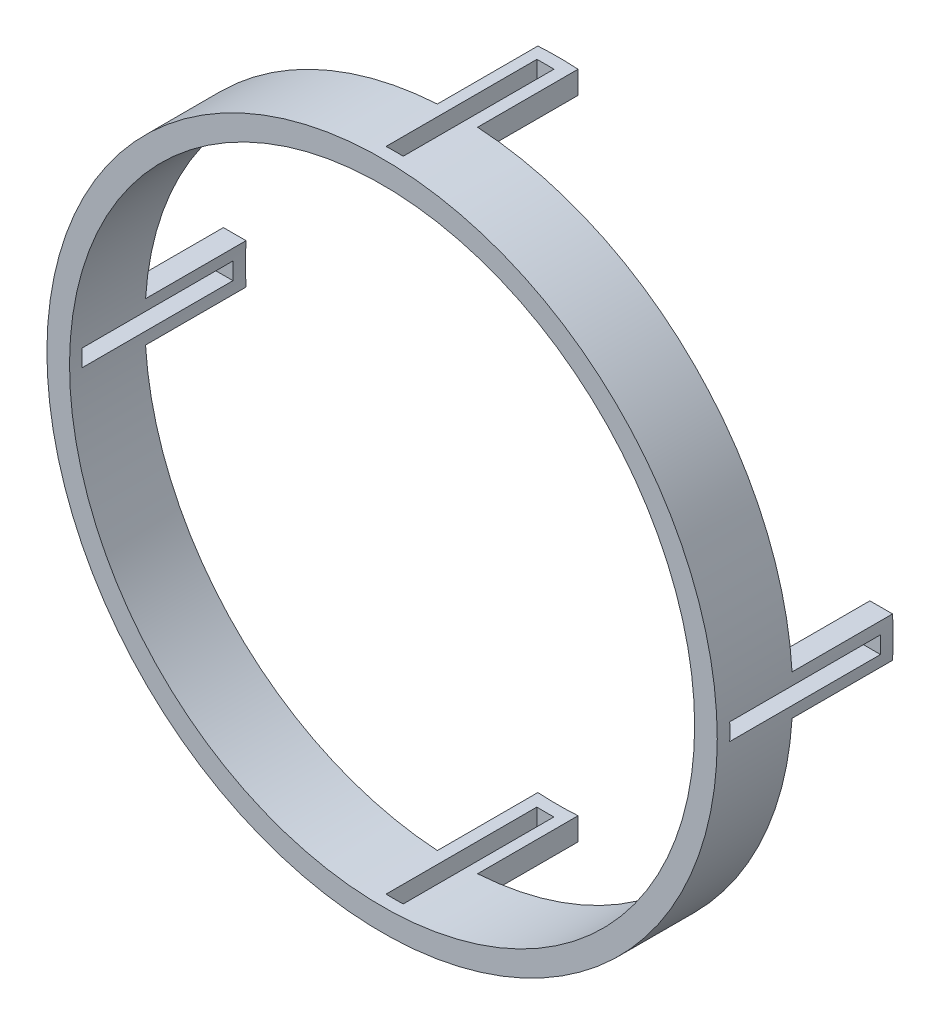
SolidWorks part; units mm, degrees
ref_plane "Front Plane" through (0, 0, 0) normal (0, 0, 1) x (1, 0, 0)
ref_plane "Top Plane" through (0, 0, 0) normal (0, 1, 0) x (1, 0, 0)
ref_plane "Right Plane" through (0, 0, 0) normal (1, 0, 0) x (0, 0, -1)
sketch "Sketch1" plane through (0, 0, 0) normal (0, 0, 1) x (1, 0, 0)
  circle A0 centre (0, 0) radius 78.994
  circle A1 centre (0, 0) radius 84.709
  dimension "D1" = 157.988
  dimension "D2" = 169.418
extrude "Boss-Extrude1" add sketch "Sketch1" along normal blind 19.05
sketch "Sketch3" plane through (0, 0, 0) normal (0, 0, -1) x (-1, 0, 0)
  line L0 (30.8173, 0) -> (-22.3005, 0) construction
  line L1 (0, -12.9993) -> (0, 95.4691) construction
  line L2 (-5.08, 78.8305) -> (-5.08, 84.5565)
  line L3 (5.08, 78.8305) -> (5.08, 84.5565)
  line L4 (-5.08, -78.8305) -> (-5.08, -84.5565)
  line L5 (5.08, -78.8305) -> (5.08, -84.5565)
  line L6 (0, 0) -> (44.2484, -44.2484) construction
  line L7 (78.8305, -5.08) -> (84.5565, -5.08)
  line L8 (78.8305, 5.08) -> (84.5565, 5.08)
  line L9 (-78.8305, 5.08) -> (-84.5565, 5.08)
  line L10 (-78.8305, -5.08) -> (-84.5565, -5.08)
  arc A0 (5.08, 78.8305) -> (-5.08, 78.8305) centre (0, 0) ccw
  circle A2 centre (0, 0) radius 78.994 construction
  arc A3 (5.08, 84.5565) -> (-5.08, 84.5565) centre (0, 0) ccw
  circle A4 centre (0, 0) radius 84.709 construction
  arc A5 (5.08, -78.8305) -> (-5.08, -78.8305) centre (0, 0) cw
  arc A6 (5.08, -84.5565) -> (-5.08, -84.5565) centre (0, 0) cw
  arc A7 (84.5565, -5.08) -> (84.5565, 5.08) centre (0, 0) ccw
  arc A8 (78.8305, -5.08) -> (78.8305, 5.08) centre (0, 0) ccw
  arc A9 (-78.8305, -5.08) -> (-78.8305, 5.08) centre (0, 0) cw
  arc A10 (-84.5565, -5.08) -> (-84.5565, 5.08) centre (0, 0) cw
  dimension "D1" = 5.08
  dimension "D2" = 5.08
  dimension "D3" = 5.08
  dimension "D4" = 5.08
  dimension "D5" = 45
extrude "Boss-Extrude2" add sketch "Sketch3" along normal blind 25.4
sketch "Sketch2" plane through (0, 0, 0) normal (0, 1, 0) x (1, 0, 0)
  line L0 (5.08, 25.4) -> (-5.08, 25.4) construction
  line L1 (0, -2.0807) -> (0, -15.8358) construction
  line L3 (-2.159, -15.875) -> (2.159, -15.875)
  line L4 (-2.159, -15.875) -> (-2.159, 22.225)
  line L5 (-2.159, 22.225) -> (2.159, 22.225)
  line L6 (2.159, -15.875) -> (2.159, 22.225)
  line L7 (-2.159, -15.875) -> (2.159, 22.225) construction
  line L8 (-2.159, 22.225) -> (2.159, -15.875) construction
  point P0 (0, 3.175)
  point P10 (0, 25.4)
  dimension "D1" = 4.318
  dimension "D2" = 38.1
  dimension "D3" = 3.175
ref_axis "Axis1" through (0, 0, 2.0807) along (0, 0, 1)
extrude "Cut-Extrude1" cut sketch "Sketch2" against normal through all
pattern_circular "CirPattern1" count 4 over 360 about axis through (0, 0, 2.0807) along (0, 0, 1) of "Cut-Extrude1"
